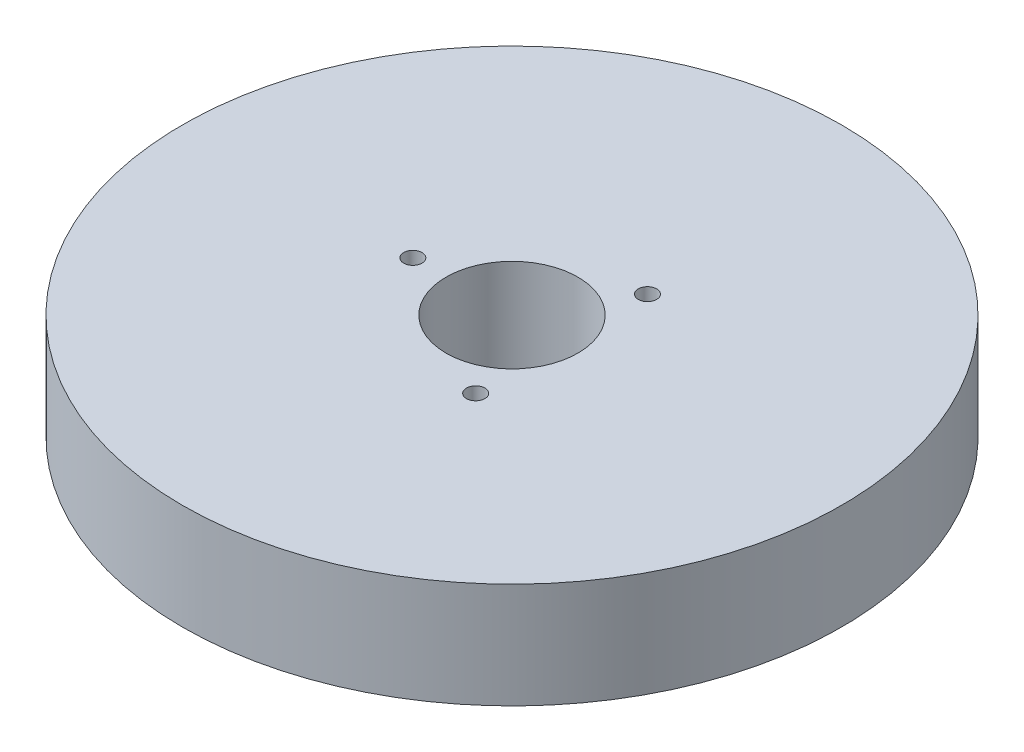
SolidWorks part; units mm, degrees
ref_plane "Front Plane" through (0, 0, 0) normal (0, 0, 1) x (1, 0, 0)
ref_plane "Top Plane" through (0, 0, 0) normal (0, 1, 0) x (1, 0, 0)
ref_plane "Right Plane" through (0, 0, 0) normal (1, 0, 0) x (0, 0, -1)
sketch "Sketch1" plane through (0, 0, 0) normal (0, 1, 0) x (1, 0, 0)
  circle A0 centre (0, 0) radius 75
  dimension "FLANGE_OD" = 150
extrude "Boss-Extrude1" add sketch "Sketch1" along normal blind 24
sketch "Sketch2" plane through (0, 0, 0) normal (0, 1, 0) x (1, 0, 0)
  circle A0 centre (0, 0) radius 15
  dimension "BORE_D" = 30
extrude "Cut-Extrude1" cut sketch "Sketch2" along normal through all
sketch "Sketch3" plane through (0, 24, 0) normal (0, 1, 0) x (1, 0, 0)
  circle A0 centre (0, 0) radius 22.5663 construction
  circle A1 centre (-22.5663, 0) radius 2.0934
  dimension "BOLT_D" = 4.1868
  dimension "BOLT_PCD" = 45.1326
extrude "Cut-Extrude2" cut sketch "Sketch3" against normal blind 22.4219
pattern_circular "CirPattern1" count 3 over 360 about axis through (0, 0, 0) along (0, 1, 0) of "Cut-Extrude2"
